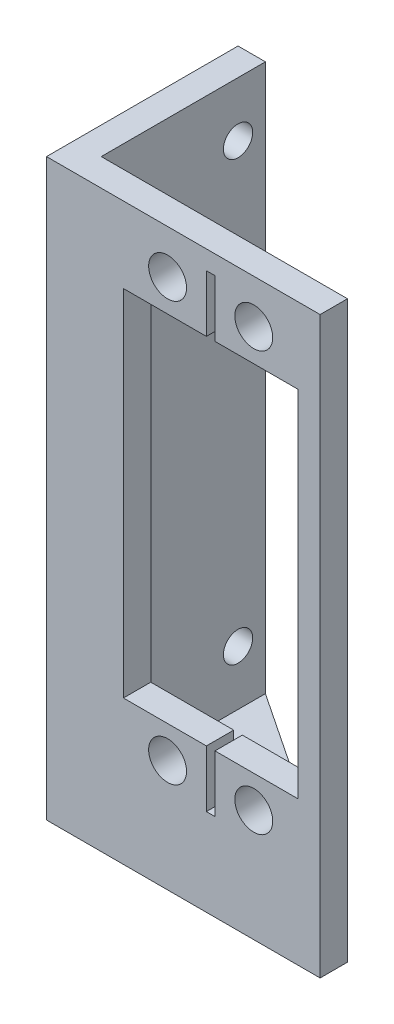
SolidWorks part; units mm, degrees
ref_plane "Front Plane" through (0, 0, 0) normal (0, 0, 1) x (1, 0, 0)
ref_plane "Top Plane" through (0, 0, 0) normal (0, 1, 0) x (1, 0, 0)
ref_plane "Right Plane" through (0, 0, 0) normal (1, 0, 0) x (0, 0, -1)
sketch "Sketch2" plane through (0, 0, 0) normal (0, 0, 1) x (1, 0, 0)
  line L1 (0, 0) -> (31.75, 0)
  line L2 (0, 0) -> (0, 63.5)
  line L3 (0, 63.5) -> (31.75, 63.5)
  line L4 (31.75, 0) -> (31.75, 63.5)
  dimension "D1" = 63.5
  dimension "D2" = 31.75
extrude "Boss-Extrude1" add sketch "Sketch2" along normal blind 3.175 contours L4 L3 L2 L1
sketch "Sketch3" plane through (0, 0, 3.175) normal (0, 0, 1) x (1, 0, 0)
  line L0 (8.923, 54.704) -> (29.177, 13.55) construction
  line L1 (8.923, 54.704) -> (18.55, 54.704)
  line L2 (8.923, 54.704) -> (8.923, 13.55)
  line L3 (8.923, 13.55) -> (18.55, 13.55)
  line L4 (29.177, 54.704) -> (29.177, 13.55)
  line L5 (29.177, 54.704) -> (8.923, 13.55) construction
  line L6 (14.05, 58.427) -> (24.05, 9.827) construction
  line L7 (14.05, 9.827) -> (24.05, 58.427) construction
  line L8 (19.55, 13.55) -> (29.177, 13.55)
  line L9 (18.55, 13.55) -> (18.55, 6.946)
  line L10 (18.55, 6.946) -> (19.55, 6.946)
  line L11 (19.55, 13.55) -> (19.55, 6.946)
  line L12 (19.05, 34.127) -> (62.1329, 34.127) construction
  line L13 (18.55, 61.308) -> (19.55, 61.308)
  line L14 (18.55, 54.704) -> (18.55, 61.308)
  line L15 (19.55, 54.704) -> (19.55, 61.308)
  line L16 (19.55, 54.704) -> (29.177, 54.704)
  line L17 (0, 0) -> (0, 63.5) construction
  line L18 (0, 63.5) -> (31.75, 63.5) construction
  circle A0 centre (14.05, 9.827) radius 2.2
  circle A1 centre (24.05, 9.827) radius 2.2
  circle A2 centre (14.05, 58.427) radius 2.2
  circle A3 centre (24.05, 58.427) radius 2.2
  point P8 (19.05, 6.946)
  point P17 (19.05, 34.127)
  point P18 (19.05, 34.127)
  point P27 (19.05, 44.45)
  dimension "D3" = 4.4
  dimension "D1" = 10
  dimension "D2" = 48.6
  dimension "D4" = 41.154
  dimension "D5" = 20.254
  dimension "D6" = 1
  dimension "D7" = 6.604
  dimension "D8" = 30.9
  dimension "D9" = 19.05
  dimension "D10" = 19.05
extrude "Cut-Extrude1" cut sketch "Sketch3" against normal through all
sketch "Sketch4" plane through (0, 0, 3.175) normal (0, 0, 1) x (1, 0, 0)
  line L0 (0, 0) -> (31.75, 0) construction
  line L1 (0, 63.5) -> (3.175, 63.5)
  line L2 (0, 63.5) -> (0, 0)
  line L3 (0, 0) -> (3.175, 0)
  line L4 (3.175, 63.5) -> (3.175, 0)
  dimension "D1" = 3.175
extrude "Boss-Extrude2" add sketch "Sketch4" against normal blind 19.05 from surface starting at face at (26.25, 9.827, 0)
sketch "Sketch5" plane through (0, 0, 0) normal (0, -1, 0) x (1, 0, 0)
  line L0 (0, 3.175) -> (31.75, 3.175)
  line L1 (31.75, 3.175) -> (31.75, 0)
  line L2 (31.75, 0) -> (3.175, -19.05)
  line L3 (3.175, -19.05) -> (0, -19.05)
  line L4 (0, -19.05) -> (0, 3.175)
extrude "Boss-Extrude3" add sketch "Sketch5" along normal blind 3.175
sketch "Sketch6" plane through (3.175, 0, 0) normal (1, 0, 0) x (0, 0, -1)
  line L0 (0, 0) -> (0, 63.5) construction
  line L1 (19.05, 0) -> (19.05, 63.5) construction
  line L2 (19.05, 63.5) -> (0, 63.5) construction
  line L4 (19.05, 0) -> (0, 0) construction
  circle A0 centre (3.175, 57.15) radius 1.7
  circle A1 centre (3.175, 6.35) radius 1.7
  circle A2 centre (15.875, 57.15) radius 1.7
  circle A3 centre (15.875, 6.35) radius 1.7
  dimension "D5" = 3.4
  dimension "D1" = 3.175
  dimension "D2" = 3.175
  dimension "D3" = 6.35
  dimension "D4" = 6.35
extrude "Cut-Extrude2" cut sketch "Sketch6" against normal through all
sketch "Sketch7" plane through (0, 0, 3.175) normal (0, 0, 1) x (1, 0, 0)
  line L0 (18.55, 54.704) -> (8.923, 54.704) construction
  line L1 (8.923, 13.55) -> (18.55, 13.55) construction
  line L2 (19.55, 61.308) -> (18.55, 61.308) construction
  point P0 (19.05, 44.45)
  point P1 (19.05, 23.804)
  point P8 (19.05, 61.308)
  dimension "D1" = 30.9
  dimension "D2" = 30.9
equation "\"D8@Sketch3\"=30.9mm"
equation "\"tighttol\" = 0.005in"
equation "\"normtol\" = 0.01in"
equation "\"loosetol\" = 0.02in"
equation "\"D5@Sketch6\"=3.4mm"
equation "\"D3@Sketch3\"=4.4mm"
equation "\"D1@Sketch7\"=30.9mm"
equation "\"D2@Sketch7\"=30.9mm"
